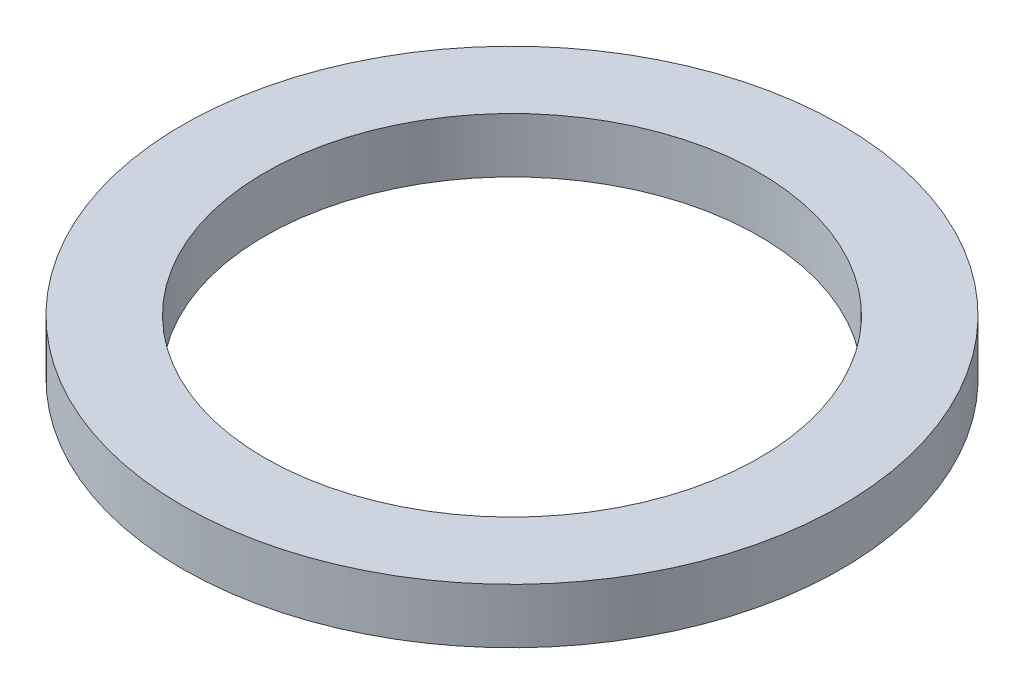
SolidWorks part; units mm, degrees
ref_plane "Front Plane" through (0, 0, 0) normal (0, 0, 1) x (1, 0, 0)
ref_plane "Top Plane" through (0, 0, 0) normal (0, 1, 0) x (1, 0, 0)
ref_plane "Right Plane" through (0, 0, 0) normal (1, 0, 0) x (0, 0, -1)
sketch "Sketch1" plane through (0, 0, 0) normal (0, 1, 0) x (1, 0, 0)
  circle A0 centre (0, 0) radius 30
  dimension "FLANGE_OD" = 60
extrude "Boss-Extrude1" add sketch "Sketch1" along normal blind 5
sketch "Sketch2" plane through (0, 0, 0) normal (0, 1, 0) x (1, 0, 0)
  circle A0 centre (0, 0) radius 22.5
  dimension "BORE_D" = 45
extrude "Cut-Extrude1" cut sketch "Sketch2" along normal through all
sketch "Sketch3" plane through (0, 5, 0) normal (0, 1, 0) x (1, 0, 0)
  circle A0 centre (0, 0) radius 13.1551 construction
  circle A1 centre (-13.1551, 0) radius 1.5
  dimension "BOLT_D" = 3
  dimension "BOLT_PCD" = 26.3103
extrude "Cut-Extrude2" cut sketch "Sketch3" against normal blind 3.3864 rebuild error yes
pattern_circular "CirPattern1" count 8 over 360 rebuild error yes
